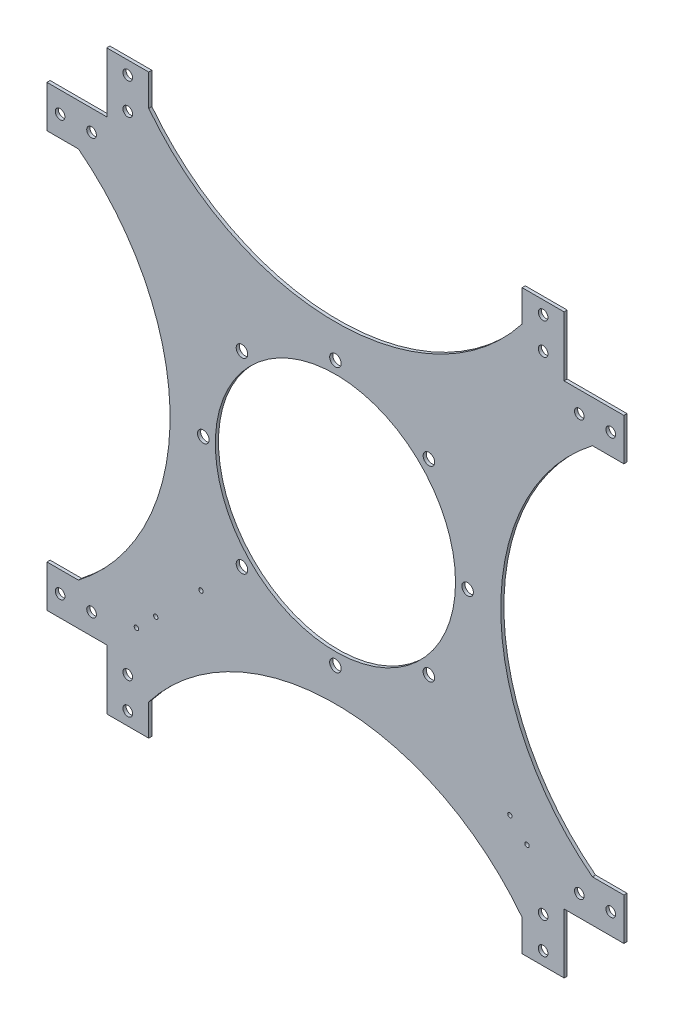
SolidWorks part; units mm, degrees
ref_plane "Front Plane" through (0, 0, 0) normal (0, 0, 1) x (1, 0, 0)
ref_plane "Top Plane" through (0, 0, 0) normal (0, 1, 0) x (1, 0, 0)
ref_plane "Right Plane" through (0, 0, 0) normal (1, 0, 0) x (0, 0, -1)
sketch "Sketch1" plane through (0, 0, 0) normal (0, 0, 1) x (1, 0, 0)
  line L0 (0, 0) -> (367.2182, 0) construction
  line L1 (0, 0) -> (0, -316.5866) construction
  line L2 (0, 0) -> (218, 218) construction
  line L3 (0, 0) -> (218, -218) construction
  line L4 (218, 218) -> (218, 275)
  line L5 (218, 218) -> (275, 218)
  line L6 (218, 275) -> (178, 275)
  line L7 (178, 275) -> (178, 245)
  line L8 (0, 0) -> (-218, 218) construction
  line L9 (0, 0) -> (-218, -218) construction
  line L10 (0, 0) -> (-199.7109, 0) construction
  line L11 (-218, 218) -> (-218, 275)
  line L12 (-218, 275) -> (-178, 275)
  line L13 (-178, 275) -> (-178, 245)
  line L14 (218, -218) -> (275, -218)
  line L15 (275, -218) -> (275, -178)
  line L16 (275, -178) -> (245, -178)
  line L17 (275, 218) -> (275, 178)
  line L18 (275, 178) -> (245, 178)
  line L19 (218, -218) -> (218, -275)
  line L20 (218, -275) -> (178, -275)
  line L21 (178, -275) -> (178, -245)
  line L22 (-178, -275) -> (-178, -245)
  line L23 (-218, -275) -> (-178, -275)
  line L24 (-218, -218) -> (-218, -275)
  line L25 (-218, -218) -> (-275, -218)
  line L26 (-275, -218) -> (-275, -178)
  line L27 (-275, -178) -> (-245, -178)
  line L28 (-275, 178) -> (-245, 178)
  line L29 (-275, 218) -> (-275, 178)
  line L30 (-218, 218) -> (-275, 218)
  circle A0 centre (0, 0) radius 114.5
  arc A1 (-178, 245) -> (178, 245) centre (0, 382.6263) ccw
  arc A2 (245, 178) -> (245, -178) centre (382.6263, 0) ccw
  arc A3 (-178, -245) -> (178, -245) centre (0, -382.6263) cw
  arc A4 (-245, 178) -> (-245, -178) centre (-382.6263, 0) cw
  dimension "D4" = 229
  dimension "D9" = 225
  dimension "D1" = 45
  dimension "D3" = 57
  dimension "D5" = 40
  dimension "D6" = 45
  dimension "D7" = 45
  dimension "D8" = 30
  dimension "D10" = 275
sheet metal parameters "Sheet-Metal1" thickness 3 parameters "D1"=1
base flange "Base-Flange1" sketch "Sketch1" thickness 3 reverse thickness direction yes parameters "D1"=1
sketch "Sketch2" plane through (0, 0, 3) normal (0, 0, 1) x (1, 0, 0)
  line L0 (218, 218) -> (218, 275) construction
  line L1 (218, 275) -> (178, 275) construction
  line L2 (275, 178) -> (275, 218) construction
  line L3 (275, 218) -> (218, 218) construction
  line L4 (0, 0) -> (260.8486, 0) construction
  line L5 (0, 0) -> (0, -250.4708) construction
  circle A0 centre (198, 262.5) radius 4.6
  circle A1 centre (198, 232.5) radius 4.6
  circle A2 centre (232.5, 198) radius 4.6
  circle A3 centre (262.5, 198) radius 4.6
  circle A4 centre (262.5, -198) radius 4.6
  circle A5 centre (232.5, -198) radius 4.6
  circle A6 centre (198, -232.5) radius 4.6
  circle A7 centre (198, -262.5) radius 4.6
  circle A8 centre (-198, -262.5) radius 4.6
  circle A9 centre (-198, -232.5) radius 4.6
  circle A10 centre (-232.5, -198) radius 4.6
  circle A11 centre (-262.5, -198) radius 4.6
  circle A12 centre (-262.5, 198) radius 4.6
  circle A13 centre (-232.5, 198) radius 4.6
  circle A14 centre (-198, 232.5) radius 4.6
  circle A15 centre (-198, 262.5) radius 4.6
  point P8 (218, 246.5)
  dimension "D2" = 9.2
  dimension "D1" = 20
  dimension "D3" = 12.5
  dimension "D4" = 30
  dimension "D5" = 30
  dimension "D6" = 12.5
  dimension "D7" = 20
extrude "Extrude1" cut sketch "Sketch2" against normal blind 3 normal cut yes
sketch "Sketch3" plane through (0, 0, 3) normal (0, 0, 1) x (1, 0, 0)
  line L0 (0, 0) -> (220.4396, 0) construction
  line L1 (0, 0) -> (0, -219.5819) construction
  line L2 (0, 0) -> (178.1909, 178.1909) construction
  circle A0 centre (0, 0) radius 126 construction
  circle A1 centre (0, 126) radius 5.5
  circle A2 centre (-126, 0) radius 5.5 construction
  circle A3 centre (0, -126) radius 5.5 construction
  circle A4 centre (126, 0) radius 5.5 construction
  dimension "D2" = 11
  dimension "D3" = 252
  dimension "D1" = 45
extrude "Extrude2" cut sketch "Sketch3" against normal blind 3 normal cut yes
pattern_circular "CirPattern1" count 8 over 360 about axis through (0, 0, 3) along (0, 0, 1) of "Extrude2"
sketch "Sketch4" plane through (0, 0, 3) normal (0, 0, 1) x (1, 0, 0)
  line L0 (-218, -218) -> (0, 0) construction
  line L1 (0, 0) -> (218, -218) construction
  circle A0 centre (-189.7157, -189.7157) radius 2.1
  circle A1 centre (-171.331, -171.331) radius 2.1
  circle A2 centre (-128.1974, -128.1974) radius 2.1
  circle A3 centre (166.3812, -166.3812) radius 2.1
  circle A4 centre (182.6447, -182.6447) radius 2.1
  dimension "D1" = 4.2
  dimension "D2" = 87
  dimension "D3" = 26
  dimension "D4" = 40
  dimension "D5" = 23
  dimension "D6" = 50
extrude "Cut-Extrude1" cut sketch "Sketch4" against normal blind 3 normal cut yes
flat pattern "Flat-Pattern1" [suppressed]
sketch "Bend-Lines1" plane through (0, 0, 0) normal (0, 1, 0) x (-1, 0, 0)
